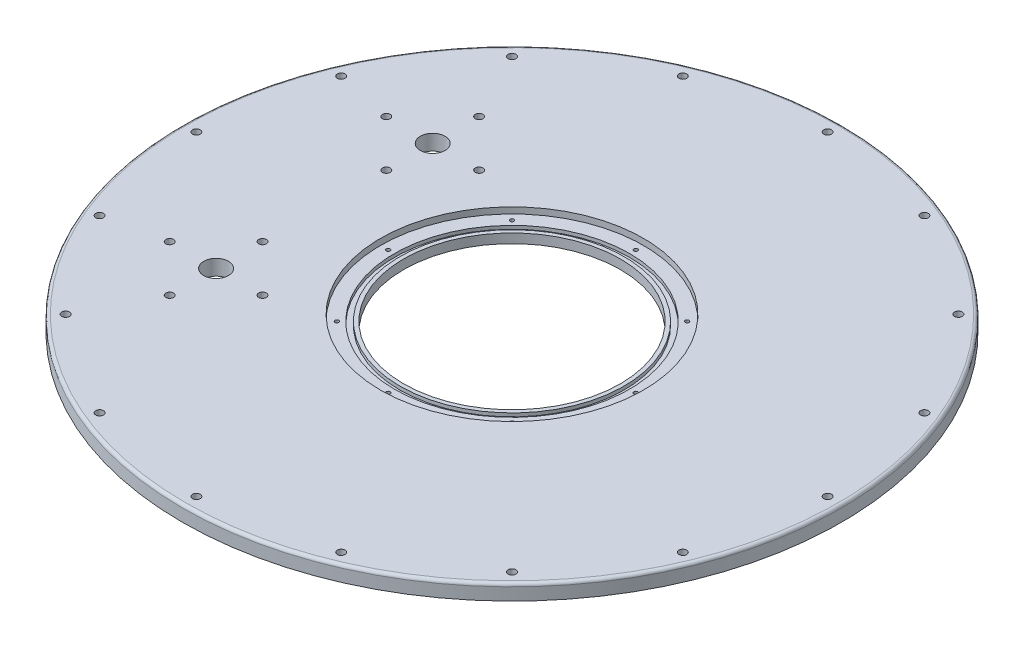
SolidWorks part; units mm, degrees
note: '?' marks a value the reader was unsure of.
ref_plane "前视基准面" through (0, 0, 0) normal (0, 0, 1) x (1, 0, 0)
ref_plane "上视基准面" through (0, 0, 0) normal (0, 1, 0) x (1, 0, 0)
ref_plane "右视基准面" through (0, 0, 0) normal (1, 0, 0) x (0, 0, -1)
sketch "草图1" plane through (0, 0, 0) normal (0, 1, 0) x (1, 0, 0)
  circle A0 centre (0, 0) radius 195
  dimension "D1" = 390
extrude "凸台-拉伸1" add sketch "草图1" along normal blind 10
sketch "草图3" plane through (0, 0, 0) normal (0, -1, 0) x (1, 0, 0)
  circle A0 centre (0, 0) radius 213
  circle A14 centre (0, 0) radius 204
  circle A16 centre (0, 0) radius 204
  circle A18 centre (0, 0) radius 204
  circle A20 centre (0, 0) radius 204
  circle A22 centre (0, 0) radius 204
  circle A24 centre (0, 0) radius 204
  circle A26 centre (0, 0) radius 204
  circle A28 centre (0, 0) radius 204
  circle A30 centre (0, 0) radius 204
  circle A32 centre (0, 0) radius 204
  circle A34 centre (0, 0) radius 204
  circle A36 centre (0, 0) radius 204
  circle A38 centre (0, 0) radius 204
  circle A40 centre (0, 0) radius 204
  circle A42 centre (0, 0) radius 204
  circle A44 centre (0, 0) radius 204
  circle A46 centre (0, 0) radius 204
  circle A48 centre (0, 0) radius 204
  circle A50 centre (0, 0) radius 204
  circle A52 centre (0, 0) radius 204
  circle A54 centre (0, 0) radius 204
  circle A56 centre (0, 0) radius 204
  circle A58 centre (0, 0) radius 204
  circle A60 centre (0, 0) radius 204
  circle A62 centre (0, 0) radius 204
  circle A64 centre (0, 0) radius 204
  circle A66 centre (0, 0) radius 204
  circle A68 centre (0, 0) radius 204
  circle A70 centre (0, 0) radius 204
  circle A72 centre (0, 0) radius 204
  point P51 (0, 0)
  point P105 (0, 0)
  point P113 (0, 0)
  dimension "D1" = 426
extrude "凸台-拉伸2" add sketch "草图3" against normal blind 10
sketch "草图20" plane through (0, 0, 0) normal (0, -1, 0) x (1, 0, 0)
  line L0 (0, 0) -> (0, 204)
  circle A0 centre (0, 0) radius 204
  dimension "D1" = 408
hole_wizard "M6 螺纹孔1" positions "3D草图4" profile "草图23" tap size "M6" standard "ISO" end condition through all
sketch3d "3D草图4"
  point P0 (0, 0, 204)
sketch "草图23" plane through (0, 0, 204) normal (1, 0, 0) x (0, 0, -1)
  line L0 (0, 0) -> (0, 10)
  line L1 (0, 10) -> (2.5, 10)
  line L2 (2.5, 10) -> (2.5, 0)
  line L5 (2.5, 0) -> (0, 0)
  line L11 (0, -6.35) -> (0, 107.95) construction
  dimension "通孔螺纹孔钻头直径" = 5
  dimension "通孔螺纹孔钻头深度" = 10
cosmetic thread "孔螺蚊线33" parameters "D2"=6
pattern_circular "阵列(圆周)1" count 16 over 360 about axis through (0, 0, 0) along (0, 1, 0) of "M6 螺纹孔1"
sketch "草图4" plane through (0, 10, 0) normal (0, 1, 0) x (1, 0, 0)
  line L0 (0, 0) -> (0, 262.2596)
sketch "草图6" plane through (0, 10, 0) normal (0, 1, 0) x (1, 0, 0)
  circle A0 centre (0, 0) radius 70
  dimension "D1" = 140
extrude "切除-拉伸2" cut sketch "草图6" against normal blind 10
sketch "草图7" plane through (0, 10, 0) normal (0, 1, 0) x (1, 0, 0)
  circle A0 centre (0, 0) radius 85
  dimension "D1" = 170
extrude "切除-拉伸3" cut sketch "草图7" against normal blind 4
sketch "草图9" plane through (0, 6, 0) normal (0, 1, 0) x (1, 0, 0)
  circle A0 centre (0, 0) radius 72.5
  circle A1 centre (0, 0) radius 76
  dimension "D1" = 145
  dimension "D2" = 152
extrude "切除-拉伸5" cut sketch "草图9" against normal blind 2.2
sketch "草图10" plane through (0, 6, 0) normal (0, 1, 0) x (1, 0, 0)
  circle A0 centre (0, 0) radius 80
  circle A1 centre (0, 80) radius 1.25
  circle A2 centre (56.5685, 56.5685) radius 1.25
  circle A3 centre (80, 0) radius 1.25
  circle A4 centre (56.5685, -56.5685) radius 1.25
  circle A5 centre (0, -80) radius 1.25
  circle A6 centre (-56.5685, -56.5685) radius 1.25
  circle A7 centre (-80, 0) radius 1.25
  circle A8 centre (-56.5685, 56.5685) radius 1.25
  point P22 (0, 0)
  dimension "D1" = 160
  dimension "D2" = 2.5
  dimension "D3" = 8
hole_wizard "M3 螺纹孔2" positions "3D草图1" profile "草图18" tap size "M3" standard "ISO"
sketch3d "3D草图1"
  point P0 (0, 6, 80)
  point P3 (56.5685, 6, 56.5685)
  point P6 (80, 6, 0)
  point P9 (56.5685, 6, -56.5685)
  point P12 (0, 6, -80)
  point P15 (-56.5685, 6, -56.5685)
  point P18 (-80, 6, 0)
  point P21 (-56.5685, 6, 56.5685)
cosmetic thread "孔螺蚊线1" parameters "D1"=3, "D2"=3
cosmetic thread "孔螺蚊线2" parameters "D1"=3, "D2"=3
cosmetic thread "孔螺蚊线3" parameters "D1"=3, "D2"=3
cosmetic thread "孔螺蚊线4" parameters "D1"=3, "D2"=3
cosmetic thread "孔螺蚊线5" parameters "D1"=3, "D2"=3
cosmetic thread "孔螺蚊线6" parameters "D1"=3, "D2"=3
cosmetic thread "孔螺蚊线7" parameters "D1"=3, "D2"=3
cosmetic thread "孔螺蚊线8" parameters "D1"=3, "D2"=3
sketch "草图18" plane through (0, 6, 80) normal (1, 0, 0) x (0, 0, 1)
  line L0 (0, 0) -> (0, 3.7511)
  line L1 (0, 3.7511) -> (1.25, 3)
  line L2 (1.25, 3) -> (1.25, 0)
  line L5 (1.25, 0) -> (0, 0)
  line L10 (0, 3.7511) -> (-1.25, 3) construction
  line L11 (0, -6.35) -> (0, 107.95) construction
  dimension "螺纹孔钻头直径" = 2.5
  dimension "螺纹孔钻头深度" = 3
  dimension "导头角度" = 118
fillet "圆角1" radius 2 1 edges at (0, 10, -213)
sketch "草图11" plane through (0, 0, 0) normal (0, -1, 0) x (1, 0, 0)
  line L0 (125, 0) -> (-125, 0)
  line L1 (0, -125) -> (0, 125)
  line L2 (0, 125) -> (-125, 125)
  circle A0 centre (-125, 125) radius 1.5
  circle A1 centre (-75, 125) radius 1.5
  circle A2 centre (-25, 125) radius 1.5
  circle A3 centre (25, 125) radius 1.5
  circle A4 centre (75, 125) radius 1.5
  circle A5 centre (125, 125) radius 1.5
  circle A6 centre (-125, 75) radius 1.5
  circle A7 centre (-75, 75) radius 1.5
  circle A8 centre (-25, 75) radius 1.5
  circle A9 centre (25, 75) radius 1.5
  circle A10 centre (75, 75) radius 1.5
  circle A11 centre (125, 75) radius 1.5
  circle A12 centre (-125, 25) radius 1.5
  circle A13 centre (-75, 25) radius 1.5
  circle A14 centre (-25, 25) radius 1.5
  circle A15 centre (25, 25) radius 1.5
  circle A16 centre (75, 25) radius 1.5
  circle A17 centre (125, 25) radius 1.5
  circle A18 centre (-125, -25) radius 1.5
  circle A19 centre (-75, -25) radius 1.5
  circle A20 centre (-25, -25) radius 1.5
  circle A21 centre (25, -25) radius 1.5
  circle A22 centre (75, -25) radius 1.5
  circle A23 centre (125, -25) radius 1.5
  circle A24 centre (-125, -75) radius 1.5
  circle A25 centre (-75, -75) radius 1.5
  circle A26 centre (-25, -75) radius 1.5
  circle A27 centre (25, -75) radius 1.5
  circle A28 centre (75, -75) radius 1.5
  circle A29 centre (125, -75) radius 1.5
  circle A30 centre (-125, -125) radius 1.5
  circle A31 centre (-75, -125) radius 1.5
  circle A32 centre (-25, -125) radius 1.5
  circle A33 centre (25, -125) radius 1.5
  circle A34 centre (75, -125) radius 1.5
  circle A35 centre (125, -125) radius 1.5
  point P4 (0, 0)
  point P7 (0, 0)
  point P31 (0, 0)
  point P55 (0, 0)
  dimension "D1" = 250
  dimension "D2" = 250
  dimension "D3" = 125
  dimension "D5" = 6
  dimension "D4" = 3
  dimension "D6" = 6
hole_wizard "M3 螺纹孔3" positions "3D草图5" profile "草图32" tap size "M3" standard "ISO"
sketch3d "3D草图5"
  point P0 (125, 0, -125)
  point P3 (75, 0, -125)
  point P6 (25, 0, -125)
  point P9 (-25, 0, -125)
  point P12 (-75, 0, -125)
  point P15 (-125, 0, -125)
  point P18 (125, 0, -75)
  point P21 (75, 0, -75)
  point P24 (125, 0, -25)
  point P27 (-75, 0, -75)
  point P30 (-125, 0, -25)
  point P33 (-125, 0, 25)
  point P36 (-75, 0, 75)
  point P39 (-75, 0, 125)
  point P42 (-125, 0, 125)
  point P45 (75, 0, 125)
  point P48 (25, 0, 125)
  point P51 (-25, 0, 125)
  point P54 (125, 0, 125)
  point P57 (125, 0, 75)
  point P60 (75, 0, 75)
  point P63 (125, 0, 25)
sketch "草图32" plane through (125, 0, -125) normal (1, 0, 0) x (0, 0, -1)
  line L0 (0, 0) -> (0, 3.9013)
  line L1 (0, 3.9013) -> (1.5, 3)
  line L2 (1.5, 3) -> (1.5, 0)
  line L5 (1.5, 0) -> (0, 0)
  line L10 (0, 3.9013) -> (-1.5, 3) construction
  line L11 (0, -6.35) -> (0, 107.95) construction
  dimension "螺纹孔钻头直径" = 3
  dimension "螺纹孔钻头深度" = 3
  dimension "导头角度" = 118
cosmetic thread "孔螺蚊线34" parameters "D1"=3, "D2"=3
cosmetic thread "孔螺蚊线35" parameters "D1"=3, "D2"=3
cosmetic thread "孔螺蚊线36" parameters "D1"=3, "D2"=3
cosmetic thread "孔螺蚊线37" parameters "D1"=3, "D2"=3
cosmetic thread "孔螺蚊线38" parameters "D1"=3, "D2"=3
cosmetic thread "孔螺蚊线39" parameters "D1"=3, "D2"=3
cosmetic thread "孔螺蚊线40" parameters "D1"=3, "D2"=3
cosmetic thread "孔螺蚊线41" parameters "D1"=3, "D2"=3
cosmetic thread "孔螺蚊线42" parameters "D1"=3, "D2"=3
cosmetic thread "孔螺蚊线43" parameters "D1"=3, "D2"=3
cosmetic thread "孔螺蚊线44" parameters "D1"=3, "D2"=3
cosmetic thread "孔螺蚊线45" parameters "D1"=3, "D2"=3
cosmetic thread "孔螺蚊线46" parameters "D1"=3, "D2"=3
cosmetic thread "孔螺蚊线47" parameters "D1"=3, "D2"=3
cosmetic thread "孔螺蚊线48" parameters "D1"=3, "D2"=3
cosmetic thread "孔螺蚊线49" parameters "D1"=3, "D2"=3
cosmetic thread "孔螺蚊线50" parameters "D1"=3, "D2"=3
cosmetic thread "孔螺蚊线51" parameters "D1"=3, "D2"=3
cosmetic thread "孔螺蚊线52" parameters "D1"=3, "D2"=3
cosmetic thread "孔螺蚊线53" parameters "D1"=3, "D2"=3
cosmetic thread "孔螺蚊线54" parameters "D1"=3, "D2"=3
cosmetic thread "孔螺蚊线55" parameters "D1"=3, "D2"=3
sketch "草图33" plane through (0, 10, 0) normal (0, 1, 0) x (1, 0, 0)
  line L0 (40.9978, 0) -> (-245.6154, 0) construction
  circle A0 centre (-121.2436, -70) radius 8
  point P7 (-121.2436, -70)
  dimension "D1" = 140
  dimension "D2" = 70
extrude "切除-拉伸6" cut sketch "草图33" against normal blind 10
ref_axis "基准轴1" through (-121.2436, 0, 70) along (0, 1, 0)?
hole_wizard "M6 螺纹孔3" positions "草图36" profile "草图37" tap size "M6" standard "ISO"
sketch "草图36" plane through (0, 10, 0) normal (0, 1, 0) x (1, 0, 0)
  point P0 (-121.2436, -100)
  dimension "D1" = 30
sketch "草图37" plane through (-121.2436, 10, 100) normal (1, 0, 0) x (0, 0, 1)
  line L0 (0, 0) -> (0, 8.0022)
  line L1 (0, 8.0022) -> (2.5, 6.5)
  line L2 (2.5, 6.5) -> (2.5, 0)
  line L5 (2.5, 0) -> (0, 0)
  line L10 (0, 8.0022) -> (-2.5, 6.5) construction
  line L11 (0, -6.35) -> (0, 107.95) construction
  dimension "螺纹孔钻头直径" = 5
  dimension "螺纹孔钻头深度" = 6.5
  dimension "导头角度" = 118
cosmetic thread "孔螺蚊线58" parameters "D1"=5, "D2"=6
pattern_circular "阵列(圆周)2" count 4 over 360 about axis through (-121.2436, 0, 70) along (0, 1, 0) of "M6 螺纹孔3"
mirror "镜向1" about plane through (0, 0, 0) normal (0, 0, 1) of "阵列(圆周)2", "M6 螺纹孔3", "切除-拉伸6"
